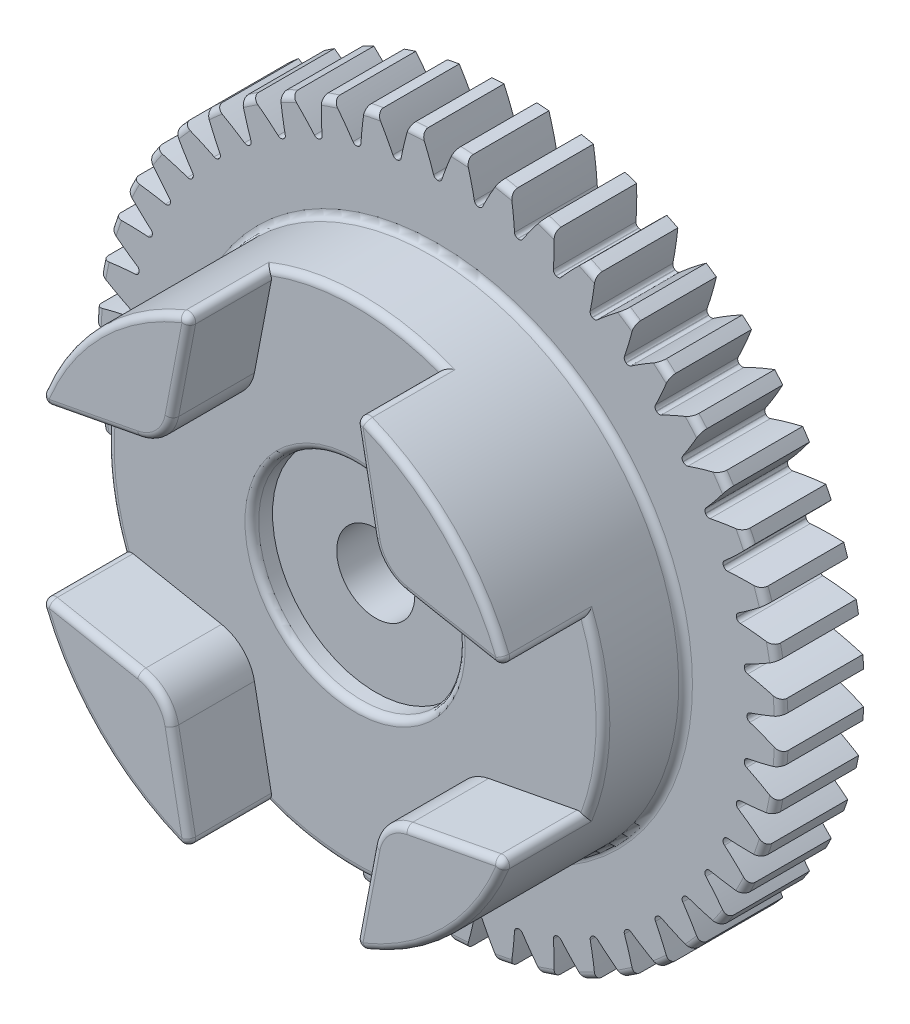
SolidWorks part; units mm, degrees
ref_plane "Front Plane" through (0, 0, 0) normal (0, 0, 1) x (1, 0, 0)
ref_plane "Top Plane" through (0, 0, 0) normal (0, 1, 0) x (1, 0, 0)
ref_plane "Right Plane" through (0, 0, 0) normal (1, 0, 0) x (0, 0, -1)
sketch "Sketch1" plane through (0, 0, 0) normal (0, 0, 1) x (1, 0, 0)
  line L0 (-609.6, 0) -> (609.6, 0) construction
  circle A0 centre (0, 0) radius 13.208 construction
  circle A1 centre (0, 0) radius 12.7 construction
  circle A2 centre (0, 0) radius 11.8851 construction
  circle A3 centre (0, 0) radius 9.525 construction
  circle A4 centre (0, 0) radius 1.5 construction
  dimension "D2" = 0.508
  dimension "D3" = 1.3229
  dimension "D1" = 1.3229
sketch "Sketch2" plane through (0, 0, 0) normal (1, 0, 0) x (0, 0, -1)
  line L0 (0, 0) -> (-3.175, 0) construction
  line L1 (-3.175, 0) -> (-9.525, 0) construction
  dimension "Overall Width" = 9.525
  dimension "Face Width" = 3.175
sketch "Sketch4" plane through (0, 0, 0) normal (1, 0, 0) x (0, 0, -1)
  line L0 (-9.525, 1.5) -> (-9.525, 9.525)
  line L1 (-9.525, 9.525) -> (-3.175, 9.525)
  line L2 (-3.175, 9.525) -> (-3.175, 13.208)
  line L3 (-3.175, 13.208) -> (0, 13.208)
  line L4 (0, 13.208) -> (0, 1.5)
  line L5 (-3.175, 9.525) -> (-3.175, 0) construction
  line L6 (0, 13.208) -> (0, -13.208) construction
  line L7 (-3.175, 9.525) -> (0, 9.525) construction
  line L12 (-9.525, 1.5) -> (0, 1.5)
revolve "Revolve1" add sketch "Sketch4" angle 360 about L1
sketch "Sketch10" plane through (0, 0, 9.525) normal (0, 0, 1) x (1, 0, 0)
  line L0 (-4.678, 0.893) -> (-2.339, 13.1465)
  line L1 (2.339, 13.1465) -> (4.678, 0.893)
  line L2 (0, 12.7) -> (0, 0) construction
  arc A0 (-4.678, 0.893) -> (4.678, 0.893) centre (0, 0) ccw
  arc A1 (-2.339, 13.1465) -> (2.339, 13.1465) centre (0, 12.7) cw
  dimension "D1" = 4.7625
  dimension "D3" = 2.3813
  dimension "D2" = 12.7
extrude "Cut-Extrude4" cut sketch "Sketch10" against normal blind 3.175
pattern_circular "CirPattern2" count 4 over 360 about axis through (0, 0, 0) along (0, 0, 1) of "Cut-Extrude4"
sketch "Sketch11" plane through (0, 0, 6.35) normal (0, 0, 1) x (1, 0, 0)
  circle A0 centre (0, 0) radius 3.9688
  dimension "D1" = 7.9375
extrude "Cut-Extrude5" cut sketch "Sketch11" against normal blind 0.7937
fillet "Fillet2" radius 0.2642 27 edges at (0, 9.525, 3.175) (0, 13.208, 3.175) (-6.7352, 6.7352, 9.525) (-3.6013, 6.5334, 9.525) (-6.5334, 3.6013, 9.525) (3.6013, 6.5334, 9.525) (6.7352, 6.7352, 9.525) (6.5334, 3.6013, 9.525) (6.7352, -6.7352, 9.525) (3.6013, -6.5334, 9.525) (6.5334, -3.6013, 9.525) (-6.7352, -6.7352, 9.525) (-6.5334, -3.6013, 9.525) (-3.6013, -6.5334, 9.525) (-8.9956, -3.1314, 7.9375) (-3.1314, -8.9956, 7.9375) (8.9956, -3.1314, 7.9375) (3.1314, -8.9956, 7.9375) (3.1314, 8.9956, 7.9375) (8.9956, 3.1314, 7.9375) (-3.1314, 8.9956, 7.9375) (-8.9956, 3.1314, 7.9375) (3.9688, 0, 6.35) (0, 9.525, 6.35) (-9.525, 0, 6.35) (9.525, 0, 6.35) (0, -9.525, 6.35)
fillet "Fillet3" radius 1.5875 8 edges at (-4.0713, -4.0713, 7.8054) (4.0713, -4.0713, 7.8054) (-4.0713, 4.0713, 7.8054) (4.0713, 4.0713, 7.8054) (4.1375, 4.1375, 9.4476) (-4.1375, 4.1375, 9.4476) (4.1375, -4.1375, 9.4476) (-4.1375, -4.1375, 9.4476)
sketch "Sketch7" plane through (0, 0, 3.175) normal (0, 0, 1) x (1, 0, 0)
  line L0 (0, 0) -> (0, 13.208) construction
  line L1 (0.4155, 12.6932) -> (0.6164, 13.1936) construction
  line L3 (0.8638, 13.1797) -> (0.8306, 12.6728) construction
  line L4 (0.8306, 12.6728) -> (0.7773, 11.8596) construction
  line L5 (0, 0) -> (0.7773, 11.8596) construction
  line L6 (0.4155, 12.6932) -> (0, 0) construction
  line L7 (0.4155, 12.6932) -> (0.4322, 13.2009) construction
  line L8 (0.4155, 12.6932) -> (0, 0) construction
  circle A0 centre (0, 0) radius 13.208 construction
  arc A1 (-0.0075, 11.8851) -> (0.0075, 11.8851) centre (0, 0) cw
  circle A2 centre (0, 0) radius 11.8851 construction
  arc A3 (-0.4155, 12.6932) -> (0.4155, 12.6932) centre (0, 0) cw construction
  circle A4 centre (0, 0) radius 12.7 construction
  arc A5 (1.0987, 13.1622) -> (0.6287, 13.193) centre (0, 0) ccw construction
  arc A6 (0.4155, 12.6932) -> (1.2448, 12.6388) centre (0, 0) cw construction
  arc A7 (-0.6287, 13.193) -> (0.6287, 13.193) centre (0, 0) cw
  arc A8 (0.1582, 11.9934) -> (0.6287, 13.193) centre (12.2011, 7.9614) cw
  arc A9 (-0.1582, 11.9934) -> (-0.6287, 13.193) centre (-12.2011, 7.9614) ccw
  arc A10 (-0.0075, 11.8851) -> (-0.1582, 11.9934) centre (-0.0076, 12.0438) cw
  arc A11 (0.0075, 11.8851) -> (0.1582, 11.9934) centre (0.0076, 12.0438) ccw
  point P26 (-0.1222, 11.8845)
  point P29 (0.1222, 11.8845)
  dimension "D4" = 0.1588
  dimension "D5" = 12.7
  dimension "D3" = 20
  dimension "D1" = 1.6624
  dimension "D2" = 0.8312
extrude "Cut-Extrude2" cut sketch "Sketch7" against normal through all
pattern_circular "CirPattern1" count 48 over 360 about axis through (0, 0, 0) along (0, 0, 1) of "Cut-Extrude2"
sketch "Sketch8" plane through (0, 0, 0) normal (0, 0, -1) x (-1, 0, 0)
  circle A0 centre (0, 0) radius 3.175
  dimension "D1" = 6.35
extrude "Cut-Extrude3" cut sketch "Sketch8" against normal blind 1.5875
equation "\"D1@Sketch1\"=2.5*(\"Pitch Dia.@Sketch1\"/\"Number of Teeth@Sketch1\")"
equation "\"D1@CirPattern1\"=\"Number of Teeth@Sketch1\""
equation "\"D1@Fillet2\"=\"OD@Sketch1\"*.01"
equation "\"D1@Sketch7\"=3.14159*(\"Pitch Dia.@Sketch1\"/\"Number of Teeth@Sketch1\")"
equation "\"D2@Sketch7\"=\"D1@Sketch7\"/2"
equation "\"D4@Sketch7\"=\"D1@Sketch7\"*.0955"
equation "\"D5@Sketch7\"=\"Pitch Dia.@Sketch1\"/2"
